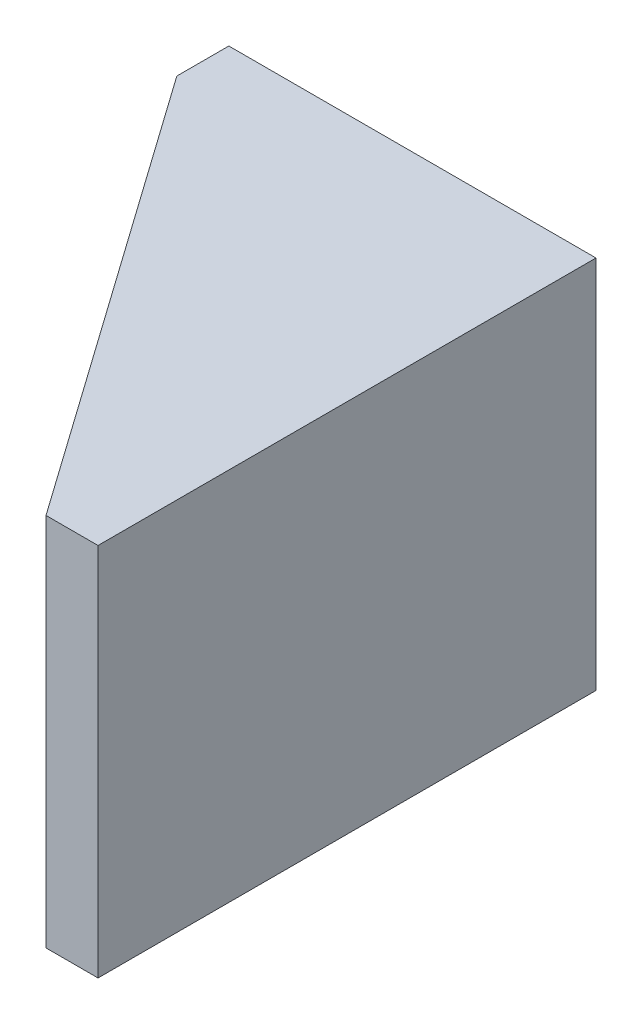
SolidWorks part; units mm, degrees
ref_plane "Front Plane" through (0, 0, 0) normal (0, 0, 1) x (1, 0, 0)
ref_plane "Top Plane" through (0, 0, 0) normal (0, 1, 0) x (1, 0, 0)
ref_plane "Right Plane" through (0, 0, 0) normal (1, 0, 0) x (0, 0, -1)
sketch "Sketch2" plane through (0, 0, 0) normal (0, 1, 0) x (1, 0, 0)
  line L0 (-42.4, 0) -> (0, 0)
  line L1 (0, 0) -> (0, -60)
  line L2 (-42.4, 0) -> (-42.4, 7)
  line L3 (-42.4, 7) -> (7, 7)
  line L4 (7, 7) -> (7, -60)
  line L5 (7, -60) -> (0, -60)
  dimension "D1" = 42.4
  dimension "D2" = 60
  dimension "D3" = 7
  dimension "D4" = 7
extrude "Boss-Extrude1" add sketch "Sketch2" along normal blind 50.4
sketch "Sketch3" plane through (0, 0, 0) normal (0, 0, 1) x (1, 0, 0)
  line L0 (-42.4, 50.4) -> (0, 0) construction
  line L2 (-36.7, 9.7) -> (-5.7, 9.7) construction
  line L3 (-36.7, 9.7) -> (-36.7, 40.7) construction
  line L4 (-36.7, 40.7) -> (-5.7, 40.7) construction
  line L5 (-5.7, 9.7) -> (-5.7, 40.7) construction
  line L6 (-36.7, 9.7) -> (-5.7, 40.7) construction
  line L7 (-36.7, 40.7) -> (-5.7, 9.7) construction
  circle A0 centre (-21.2, 25.2) radius 11.5
  circle A1 centre (-36.7, 40.7) radius 1.5
  circle A2 centre (-5.7, 40.7) radius 1.5
  circle A3 centre (-5.7, 9.7) radius 1.5
  circle A4 centre (-36.7, 9.7) radius 1.5
  dimension "D1" = 23
  dimension "D2" = 3
  dimension "D3" = 31
extrude "Cut-Extrude1" cut sketch "Sketch3" against normal through all
sketch "Sketch4" plane through (0, 50.4, 0) normal (0, 1, 0) x (1, 0, 0)
  line L0 (-42.4, 7) -> (7, 7)
  line L1 (7, 7) -> (7, -60)
  line L2 (7, -60) -> (0, -60)
  line L3 (0, -60) -> (-42.4, 0)
  line L4 (-42.4, 0) -> (-42.4, 7)
extrude "Boss-Extrude2" add sketch "Sketch4" against normal blind 4 contours L3 L4 L0 L1 L2
ref_plane "Plane1" through (0, 25.2, 0) normal (0, 1, 0) x (1, 0, 0)
mirror "Mirror1" about plane through (0, 25.2, 0) normal (0, 1, 0) of "Boss-Extrude2"
